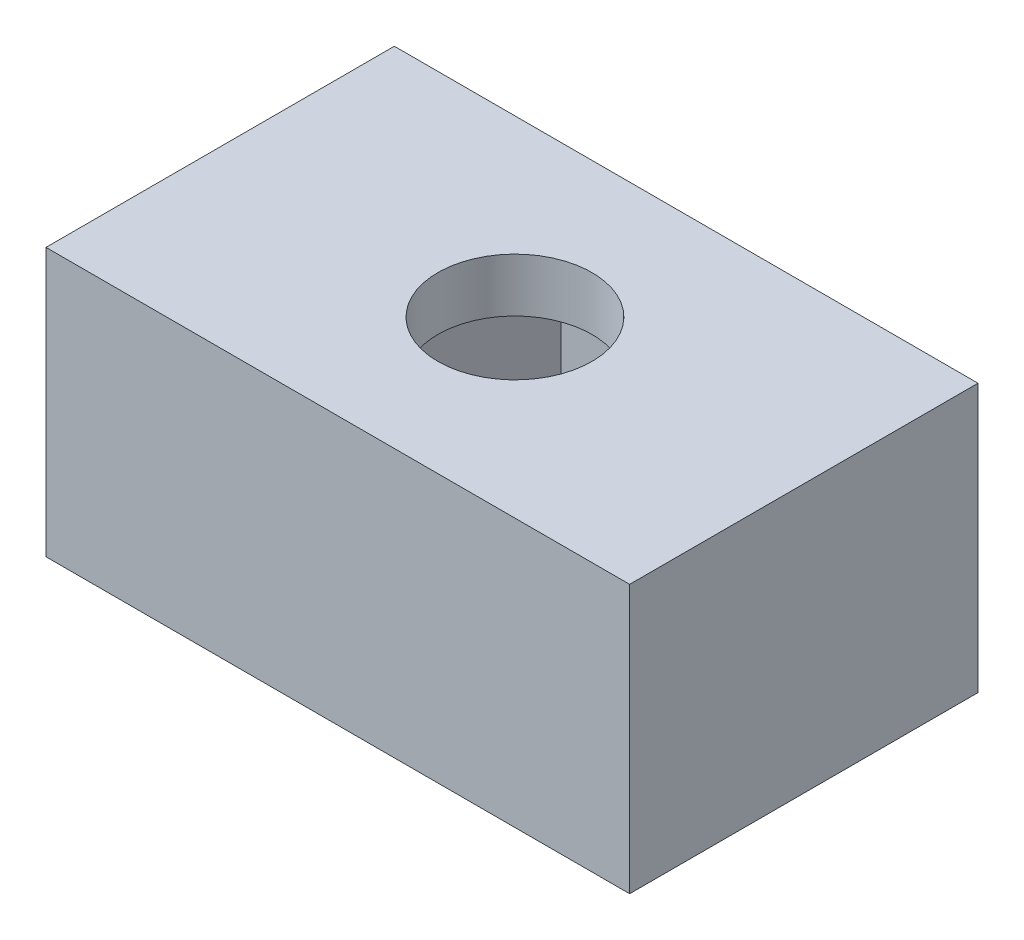
SolidWorks part; units mm, degrees
ref_plane "Front" through (0, 0, 0) normal (0, 0, 1) x (1, 0, 0)
ref_plane "Top" through (0, 0, 0) normal (0, 1, 0) x (1, 0, 0)
ref_plane "Right" through (0, 0, 0) normal (1, 0, 0) x (0, 0, -1)
sketch "Croquis1" plane through (0, 0, 0) normal (0, 1, 0) x (1, 0, 0)
  line L0 (-16, 0) -> (16, 0)
  line L1 (-27, 6.5) -> (27, 6.5)
  line L2 (-27, 6.5) -> (-27, -6.5)
  line L3 (-27, -6.5) -> (27, -6.5)
  line L4 (27, 6.5) -> (27, -6.5)
  line L5 (-27, 6.5) -> (27, -6.5) construction
  line L6 (-27, -6.5) -> (27, 6.5) construction
  line L8 (-18.3383, -4.05) -> (-13.6617, -4.05)
  line L9 (-13.6617, -4.05) -> (-11.3235, 0)
  line L10 (-11.3235, 0) -> (-13.6617, 4.05)
  line L11 (-13.6617, 4.05) -> (-18.3383, 4.05)
  line L12 (-18.3383, 4.05) -> (-20.6765, 0)
  line L13 (-20.6765, 0) -> (-18.3383, -4.05)
  line L14 (20.6765, 0) -> (18.3383, 4.05)
  line L15 (18.3383, 4.05) -> (13.6617, 4.05)
  line L16 (13.6617, 4.05) -> (11.3235, 0)
  line L17 (11.3235, 0) -> (13.6617, -4.05)
  line L18 (13.6617, -4.05) -> (18.3383, -4.05)
  line L19 (18.3383, -4.05) -> (20.6765, 0)
  circle A0 centre (-16, 0) radius 4.05 construction
  circle A1 centre (16, 0) radius 4.05 construction
  circle A2 centre (-16, 0) radius 2.875
  circle A3 centre (16, 0) radius 2.875
  point P0 (0, 0)
  point P9 (0, 0)
  dimension "D5" = 5.75
  dimension "D6" = 5.75
  dimension "D1" = 13
  dimension "D2" = 32
  dimension "D3" = 54
  dimension "D4" = 8.1
extrude "Saliente-Extruir1" add sketch "Croquis1" along normal blind 10 contours L3 L4 L1 L2
extrude "Cortar-Extruir1" cut sketch "Croquis1<3>" along normal blind 8 contours L8 L9 L10 L11 L12 L13 | L14 L15 L16 L17 L18 L19
sketch "Croquis1<3>" plane through (0, 0, 0) normal (0, 1, 0) x (1, 0, 0) same geometry as "Croquis1"
extrude "Cortar-Extruir2" cut sketch "Croquis1<4>" along normal through all contours A2 | A3
sketch "Croquis1<4>" plane through (0, 0, 0) normal (0, 1, 0) x (1, 0, 0) same geometry as "Croquis1"
ref_plane "Plano1" through (-5.22, 0, 0) normal (-1, 0, 0) x (0, 0, 1)
sketch "Croquis2" plane through (-5.22, 0, 0) normal (-1, 0, 0) x (0, 0, 1)
  line L1 (26.3105, -8.3708) -> (-24.5766, -8.3708)
  line L2 (26.3105, -8.3708) -> (26.3105, 19.2918)
  line L3 (26.3105, 19.2918) -> (-24.5766, 19.2918)
  line L4 (-24.5766, -8.3708) -> (-24.5766, 19.2918)
  line L5 (26.3105, -8.3708) -> (-24.5766, 19.2918) construction
  line L6 (26.3105, 19.2918) -> (-24.5766, -8.3708) construction
  point P0 (0.8669, 5.4605)
extrude "Cortar-Extruir3" cut sketch "Croquis2" against normal through all
